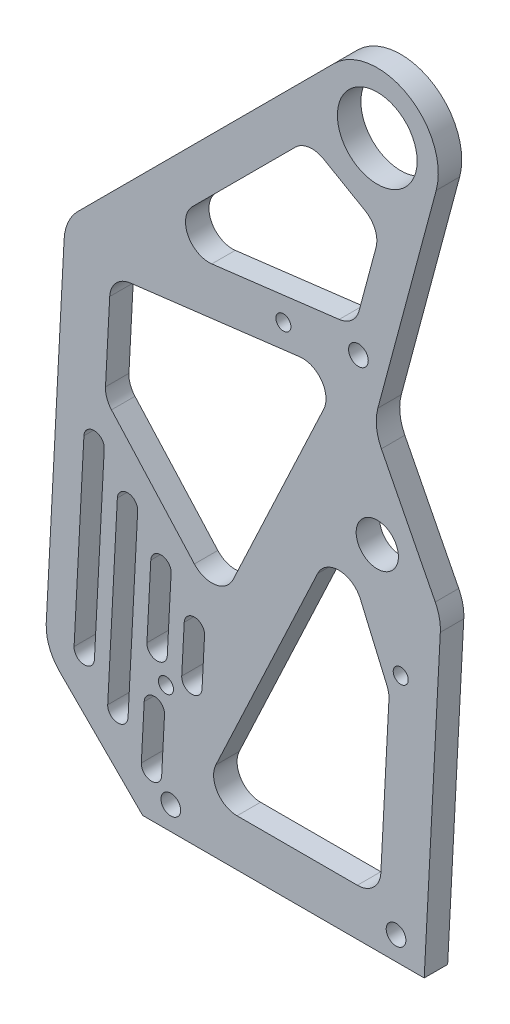
SolidWorks part; units mm, degrees
material "6061 Alloy"
ref_plane "Front Plane" through (0, 0, 0) normal (0, 0, 1) x (1, 0, 0)
ref_plane "Top Plane" through (0, 0, 0) normal (0, 1, 0) x (1, 0, 0)
ref_plane "Right Plane" through (0, 0, 0) normal (1, 0, 0) x (0, 0, -1)
sketch "Sketch1" plane through (0, 0, 0) normal (0, 0, 1) x (1, 0, 0)
  line L0 (0, 103.759) -> (0, -103.759) construction
  line L1 (-30, 76) -> (50, 76)
  line L2 (-30, 76) -> (-30, 256)
  line L3 (-30, 256) -> (50, 256)
  line L4 (50, 76) -> (50, 256)
  circle A0 centre (20, 226) radius 8.5
  dimension "D1" = 150
  dimension "D5" = 17
  dimension "D2" = 20
  dimension "D3" = 180
  dimension "D4" = 80
extrude "Boss-Extrude1" add sketch "Sketch1" along normal blind 5
sketch "Sketch2" plane through (0, 0, 5) normal (0, 0, 1) x (1, 0, 0)
  line L0 (20, 226) -> (20, 151) construction
  line L1 (20, 226) -> (-17.1819, 226) construction
  circle A0 centre (20, 151) radius 4.5
  dimension "D3" = 9
  dimension "D1" = 75
  dimension "D2" = 90
extrude "Cut-Extrude1" cut sketch "Sketch2" against normal blind 30
sketch "Sketch3" plane through (0, 0, 5) normal (0, 0, 1) x (1, 0, 0)
  circle A0 centre (0, 182) radius 1.6
  circle A1 centre (25, 129.3013) radius 1.6
  circle A2 centre (-25.0329, 102.5335) radius 1.6
  circle A3 centre (-15, 81) radius 2.5
  circle A4 centre (15, 81) radius 2.5
  circle A5 centre (24, 91) radius 2.5
  circle A6 centre (-24, 91) radius 2.5
  dimension "D1" = 5
  dimension "D2" = 3.2
extrude "Cut-Extrude2" cut sketch "Sketch3" against normal blind 5
sketch "Sketch4" plane through (0, 0, 5) normal (0, 0, 1) x (1, 0, 0)
  line L0 (10.8076, 235.1924) -> (-46.0411, 178.3437)
  line L1 (-46.0411, 178.3437) -> (-46.0411, 109.8941)
  line L2 (-46.0411, 109.8941) -> (-30, 76)
  line L3 (32.557, 222.6354) -> (22.7869, 186.1729)
  line L4 (22.7869, 186.1729) -> (30, 173.6795)
  line L5 (30, 173.6795) -> (30, 76)
  line L6 (-30, 76) -> (50, 76) construction
  line L7 (30, 76) -> (50, 76)
  line L8 (50, 76) -> (50, 256)
  line L9 (50, 256) -> (-30, 256)
  line L10 (-30, 256) -> (-68.6435, 166)
  line L11 (-68.6435, 166) -> (-57.2516, 84.4416)
  line L12 (-57.2516, 84.4416) -> (-30, 76)
  circle A0 centre (20, 226) radius 13
  circle A1 centre (20, 151) radius 4.5 construction
  line M14 (-30, 256) -> (-30, 76)
  line M15 (-30, 76) -> (50, 76)
  line M16 (50, 76) -> (50, 256)
  line M17 (50, 256) -> (-30, 256)
  dimension "D1" = 26
  dimension "D4" = 20
  dimension "D5" = 60
  dimension "D2" = 75
  dimension "D3" = 45
  dimension "D6" = 60
extrude "Cut-Extrude3" cut sketch "Sketch4" against normal blind 10 contours A0 L3 L4 L5 L0 M15 M16 M17 M14 region at (-10.989, 216.1814, 5)
sketch "Sketch5" plane through (0, 0, 5) normal (0, 0, 1) x (1, 0, 0)
  line L0 (-30, 194.3848) -> (-46.5355, 177.8492)
  line L1 (-48, 174.3137) -> (-48, 96.0711)
  line L2 (-46.5355, 92.5355) -> (-30, 76)
  line L4 (10.8076, 235.1924) -> (-30, 194.3848) construction
  line L6 (-30, 194.3848) -> (-30, 76) construction
  line L15 (-30, 76) -> (30, 76) construction
  line L16 (-35, 169.3848) -> (-35, 101) construction
  line L17 (-30, 169.3848) -> (-30, 101)
  line L18 (-40, 169.3848) -> (-40, 101)
  line L19 (-30, 138.6777) -> (-30, 121.7071)
  line L20 (-30, 138.6777) -> (-40, 148.6777)
  line L21 (-30, 121.7071) -> (-40, 131.7071)
  line L22 (-40, 148.6777) -> (-40, 131.7071)
  line L23 (-40, 148.6777) -> (-30, 121.7071)
  arc A0 (-30, 169.3848) -> (-40, 169.3848) centre (-35, 169.3848) ccw
  arc A1 (-40, 101) -> (-30, 101) centre (-35, 101) ccw
  arc A2 (-48, 96.0711) -> (-46.5355, 92.5355) centre (-43, 96.0711) ccw
  arc A3 (-46.5355, 177.8492) -> (-48, 174.3137) centre (-43, 174.3137) ccw
  point P14 (-35, 135.1924)
  point P26 (-48, 94)
  point P29 (-48, 176.3848)
  line M19 (-30, 194.3848) -> (-30, 76)
  dimension "D6" = 5
  dimension "D9" = 5
  dimension "D1" = 18
  dimension "D2" = 45
  dimension "D3" = 7
  dimension "D4" = 7
  dimension "D5" = 8
  dimension "D7" = 12
  dimension "D8" = 135
extrude "Boss-Extrude2" add sketch "Sketch5" against normal blind 5 contours L1 L2 L0 A1 L18 A0 L17 M19 | L16 L23 L18 L21 | L20 L16 L23 L17 | L16 L20 L23 | L23 L16 L21 region at (-40.982, 135.1924, 5) region at (-32.2222, 134.3002, 5) region at (-33.3333, 127.8689, 5) region at (-36.6667, 142.5159, 5) region at (-37.7778, 136.0845, 5)
fillet "Fillet1" radius 2 4 edges at (-40, 131.7071, 2.5) (-40, 148.6777, 2.5) (-30, 121.7071, 2.5) (-30, 138.6777, 2.5)
fillet "Fillet2" radius 5 2 edges at (30, 173.6795, 2.5) (22.7869, 186.1729, 2.5)
sketch "Sketch6" plane through (0, 0, 5) normal (0, 0, 1) x (1, 0, 0)
  line L0 (32.557, 222.6354) -> (23.323, 188.1734) construction
  line L1 (23.8225, 184.3793) -> (29.3301, 174.8397) construction
  circle A0 centre (15.9821, 183.9592) radius 2.1
  dimension "D1" = 4.2
  dimension "D2" = 6
  dimension "D3" = 7
extrude "Cut-Extrude4" cut sketch "Sketch6" against normal blind 5
sketch "Sketch7" plane through (0, 0, 5) normal (0, 0, 1) x (1, 0, 0)
  line L0 (30, 172.3397) -> (30, 76) construction
  line L1 (-30, 76) -> (30, 76)
  line L2 (-30, 76) -> (-30, 95.778)
  line L3 (-30, 95.778) -> (30, 95.778)
  line L4 (30, 76) -> (30, 95.778)
extrude "Boss-Extrude3" add sketch "Sketch7" against normal blind 5
sketch "Sketch8" plane through (0, 0, 5) normal (0, 0, 1) x (1, 0, 0)
  line L0 (-30, 169.3848) -> (-30, 143.5061) construction
  line L1 (-30, 76) -> (30, 76) construction
  circle A0 centre (-24, 81) radius 2.1
  circle A1 centre (24, 81) radius 2.1
  dimension "D1" = 4.2
  dimension "D2" = 6
  dimension "D3" = 54
  dimension "D4" = 5
extrude "Cut-Extrude6" cut sketch "Sketch8" against normal blind 5
sketch "Sketch9" plane through (0, 0, 5) normal (0, 0, 1) x (1, 0, 0)
  line L0 (18.046, 201.8387) -> (15.6185, 192.779)
  line L1 (1.2774, 211.52) -> (-13.5494, 196.6932)
  line L2 (11.0087, 189.078) -> (-9.7941, 188.1625)
  line L3 (-40, 126.8787) -> (-40, 101) construction
  arc A0 (8.1878, 211.6737) -> (14.7239, 207.9001) centre (20, 224.5858) ccw
  arc A1 (8.1878, 211.6737) -> (1.2774, 211.52) centre (4.8129, 207.9845) ccw
  arc A2 (14.7239, 207.9001) -> (18.046, 201.8387) centre (13.2164, 203.1328) cw
  arc A3 (-13.5494, 196.6932) -> (-9.7941, 188.1625) centre (-10.0139, 193.1577) ccw
  arc A4 (15.6185, 192.779) -> (11.0087, 189.078) centre (10.7889, 194.0731) cw
  dimension "D1" = 17.5
  dimension "D2" = 5
  dimension "D3" = 26.4506
  dimension "D4" = 29.9861
  dimension "D5" = 30.2059
  dimension "D6" = 41.2774
  dimension "D7" = 48.1878
  dimension "D8" = 50.7889
  dimension "D9" = 53.2164
  dimension "D10" = 18.7778
extrude "Cut-Extrude7" cut sketch "Sketch9" against normal blind 5
sketch "Sketch10" plane through (0, 0, 5) normal (0, 0, 1) x (1, 0, 0)
  line L0 (-20, 175.0528) -> (-20, 110.5916)
  line L1 (-20, 110.5916) -> (16.0369, 175.0528)
  line L2 (16.0369, 175.0528) -> (-20, 175.0528)
  line L3 (12.3296, 143.8296) -> (-20, 86)
  line L4 (-20, 86) -> (18, 86)
  line L5 (18, 86) -> (18, 140.6922)
  line L7 (-30, 76) -> (30, 76) construction
  line L8 (-30, 169.3848) -> (-30, 143.5061) construction
  line L9 (30, 172.3397) -> (30, 76) construction
  arc A0 (12.3296, 143.8296) -> (18, 140.6922) centre (20, 151) ccw
  circle A1 centre (20, 151) radius 4.5 construction
  circle A2 centre (20, 151) radius 4.5 construction
  dimension "D5" = 6
  dimension "D1" = 10
  dimension "D2" = 12
  dimension "D3" = 10
  dimension "D4" = 12
extrude "Cut-Extrude8" cut sketch "Sketch10" against normal blind 10
fillet "Fillet3" radius 5 5 edges at (18, 86, 2.5) (-20, 86, 2.5) (-20, 110.5916, 2.5) (16.0369, 175.0528, 2.5) (-20, 175.0528, 2.5)
fillet "Fillet4" radius 3 2 edges at (18, 140.6922, 2.5) (12.3296, 143.8296, 2.5)
sketch "Sketch11" plane through (0, 0, 5) normal (0, 0, 1) x (1, 0, 0)
  line L0 (23.323, 188.1734) -> (19.1312, 172.5294)
  line L1 (19.1312, 172.5294) -> (33.5734, 144.1849)
  line L2 (33.5734, 144.1849) -> (30, 76)
  line L3 (30, 76) -> (30, 151.1981)
  line L4 (30, 172.3397) -> (30, 76) construction
  line L5 (-46.5355, 177.8492) -> (-50.784, 96.784)
  line L6 (-50.784, 96.784) -> (-46.5355, 92.5355)
  line L7 (-46.5355, 92.5355) -> (-46.5355, 177.8492)
  line L8 (32.557, 222.6354) -> (23.323, 188.1734) construction
  line L9 (-46.5355, 92.5355) -> (-30, 76) construction
  circle A0 centre (20, 151) radius 4.5 construction
  dimension "D1" = 3
  dimension "D2" = 9
  dimension "D3" = 30
extrude "Boss-Extrude4" add sketch "Sketch11" against normal blind 5 contours L3 L2 L1 | L6 L7 L5 region at (31.1911, 123.7943, 5) region at (-47.9517, 122.3896, 5)
sketch "Sketch12" plane through (0, 0, 5) normal (0, 0, 1) x (1, 0, 0)
  line L0 (-48, 149.9056) -> (-46.5355, 177.8492)
  line L1 (10.8076, 235.1924) -> (-46.5355, 177.8492) construction
  line L2 (-46.5355, 177.8492) -> (-48, 176.3848)
  line L3 (-48, 176.3848) -> (-48, 149.9056)
  line L4 (-48, 174.3137) -> (-48, 149.9056) construction
  line L5 (-48, 149.9056) -> (-50.784, 96.784) construction
  line L6 (23.323, 188.1734) -> (19.1312, 172.5294)
  line L7 (19.1312, 172.5294) -> (30, 151.1981)
  line L8 (30, 151.1981) -> (30, 213.0924)
  line L9 (32.557, 222.6354) -> (23.323, 188.1734) construction
  line L10 (30, 213.0924) -> (23.323, 188.1734)
  line L11 (30, 151.1981) -> (33.5734, 144.1849) construction
extrude "Cut-Extrude9" cut sketch "Sketch12" against normal blind 5
sketch "Sketch13" plane through (0, 0, 5) normal (0, 0, 1) x (1, 0, 0)
  line L0 (-11.4765, 86) -> (13, 86) construction
  line L1 (18, 91) -> (18, 138.4601) construction
  line L2 (10.6232, 140.7773) -> (-15.8408, 93.4399) construction
  line L3 (-10.6357, 127.3421) -> (11.8776, 167.6129) construction
  line L4 (-20, 170.0528) -> (-20, 129.7819) construction
  line L5 (7.5133, 175.0528) -> (-15, 175.0528) construction
  line L6 (-9.7941, 188.1625) -> (11.0087, 189.078) construction
  line L7 (15.6185, 192.779) -> (18.046, 201.8387) construction
  line L8 (1.2774, 211.52) -> (-13.5494, 196.6932) construction
  line L9 (-20, 86) -> (18, 86)
  line L10 (18, 86) -> (18, 140.6922)
  line L11 (12.3296, 143.8296) -> (-20, 86)
  line L12 (-20, 110.5916) -> (16.0369, 175.0528)
  line L13 (-20, 175.0528) -> (-20, 110.5916)
  line L14 (16.0369, 175.0528) -> (-20, 175.0528)
  line L15 (-22.6456, 187.597) -> (14.67, 189.2391)
  line L16 (14.67, 189.2391) -> (19.4543, 207.0943)
  line L17 (5.1248, 215.3674) -> (-22.6456, 187.597)
  line L18 (-30, 169.3848) -> (-30, 143.5061) construction
  line L19 (-40, 169.3848) -> (-40, 149.5061) construction
  line L20 (-30, 169.3848) -> (-30, 101)
  line L21 (-40, 169.3848) -> (-40, 101)
  arc A0 (8.1878, 211.6737) -> (14.7239, 207.9001) centre (20, 224.5858) ccw construction
  arc A1 (5.1248, 215.3674) -> (19.4543, 207.0943) centre (20, 224.5858) ccw
  arc A2 (-40, 101) -> (-30, 101) centre (-35, 101) ccw construction
  arc A3 (-30, 169.3848) -> (-40, 169.3848) centre (-35, 169.3848) ccw construction
  arc A4 (-40, 101) -> (-30, 101) centre (-35, 101) ccw
  arc A5 (-30, 169.3848) -> (-40, 169.3848) centre (-35, 169.3848) ccw
  arc A6 (14.7436, 141.9104) -> (16.1111, 141.2467) centre (20, 151) ccw construction
  arc A7 (12.3296, 143.8296) -> (18, 140.6922) centre (20, 151) ccw
extrude "Boss-Extrude5" add sketch "Sketch13" against normal blind 5
sketch "Sketch14" plane through (0, 0, 5) normal (0, 0, 1) x (1, 0, 0)
  line L0 (5.2684, 218.3395) -> (-29.6708, 183.4002)
  line L1 (-29.6708, 183.4002) -> (15.2369, 188.9052)
  line L2 (15.2369, 188.9052) -> (20.7316, 209.4118)
  line L3 (20.7316, 209.4118) -> (5.2684, 218.3395)
  line L4 (-36.8047, 172.4509) -> (-38.0295, 149.0806)
  line L5 (-38.0295, 149.0806) -> (-13.9428, 122.3296)
  line L6 (-13.9428, 122.3296) -> (12.4456, 178.4882)
  line L7 (12.4456, 178.4882) -> (-36.8047, 172.4509)
  line L8 (12.0058, 149.3354) -> (-17.755, 86)
  line L9 (-17.755, 86) -> (20.5104, 86)
  line L10 (20.5104, 86) -> (22.5482, 124.885)
  line L11 (22.5482, 124.885) -> (12.0058, 149.3354)
  line L12 (33.5734, 144.1849) -> (30, 76) construction
  line L13 (10.8076, 235.1924) -> (-46.5355, 177.8492) construction
  line L14 (32.557, 222.6354) -> (19.1312, 172.5294) construction
  line L15 (-46.5355, 177.8492) -> (-50.784, 96.784) construction
  line L16 (20, 226) -> (13, 213.8756) construction
  line L17 (0, 182) -> (-0.6084, 186.9629) construction
  line L18 (0, 182) -> (0.6084, 177.0371) construction
  line L19 (15.9821, 183.9592) -> (15.3738, 188.922) construction
  line L20 (15.9821, 183.9592) -> (16.5905, 178.9963) construction
  line L21 (-30, 76) -> (30, 76) construction
  line L22 (-40.3533, 139.7057) -> (-42.4468, 99.7605) construction
  line L23 (-38.1863, 139.5921) -> (-40.2798, 99.6469)
  line L24 (-42.5204, 139.8192) -> (-44.6138, 99.8741)
  line L25 (-33.2278, 131.7919) -> (-35.2819, 92.5956) construction
  line L26 (-31.0607, 131.6783) -> (-33.1149, 92.4821)
  line L27 (-35.3948, 131.9055) -> (-37.449, 92.7092)
  line L28 (-27.5072, 97.0675) -> (-28.1171, 85.4308) construction
  line L29 (-25.3402, 96.9539) -> (-25.9501, 85.3172)
  line L30 (-29.6743, 97.181) -> (-30.2841, 85.5444)
  line L31 (-40.7876, 131.4195) -> (-33.2679, 131.0254) construction
  line L32 (-33.2679, 131.0254) -> (-25.7482, 130.6313) construction
  line L33 (-26.1022, 123.8781) -> (-26.9223, 108.2282) construction
  line L34 (-23.9351, 123.7646) -> (-24.7553, 108.1146)
  line L35 (-28.2692, 123.9917) -> (-29.0894, 108.3418)
  line L36 (-18.9766, 115.9644) -> (-19.5104, 105.7781) construction
  line L37 (-16.8095, 115.8508) -> (-17.3434, 105.6646)
  line L38 (-21.1436, 116.0779) -> (-21.6774, 105.8917)
  line L39 (-26.2388, 121.2703) -> (-18.7191, 120.8762) construction
  line L40 (-40.3533, 139.7057) -> (-18.9766, 115.9644) construction
  line L41 (-42.4468, 99.7605) -> (-28.1171, 85.4308) construction
  line L42 (-50.784, 96.784) -> (-30, 76) construction
  circle A0 centre (20, 226) radius 8.5 construction
  circle A2 centre (-24, 81) radius 2.1 construction
  circle A3 centre (20, 151) radius 4.5 construction
  circle A4 centre (25, 129.3013) radius 1.6 construction
  arc A5 (-38.1863, 139.5921) -> (-42.5204, 139.8192) centre (-40.3533, 139.7057) ccw
  arc A6 (-44.6138, 99.8741) -> (-40.2798, 99.6469) centre (-42.4468, 99.7605) ccw
  arc A7 (-31.0607, 131.6783) -> (-35.3948, 131.9055) centre (-33.2278, 131.7919) ccw
  arc A8 (-37.449, 92.7092) -> (-33.1149, 92.4821) centre (-35.2819, 92.5956) ccw
  arc A9 (-25.3402, 96.9539) -> (-29.6743, 97.181) centre (-27.5072, 97.0675) ccw
  arc A10 (-30.2841, 85.5444) -> (-25.9501, 85.3172) centre (-28.1171, 85.4308) ccw
  arc A11 (-23.9351, 123.7646) -> (-28.2692, 123.9917) centre (-26.1022, 123.8781) ccw
  arc A12 (-29.0894, 108.3418) -> (-24.7553, 108.1146) centre (-26.9223, 108.2282) ccw
  arc A13 (-16.8095, 115.8508) -> (-21.1436, 116.0779) centre (-18.9766, 115.9644) ccw
  arc A14 (-21.6774, 105.8917) -> (-17.3434, 105.6646) centre (-19.5104, 105.7781) ccw
  circle A15 centre (-25.0329, 102.5335) radius 1.6 construction
  point P33 (-41.4001, 119.7331)
  point P40 (-34.2548, 112.1938)
  point P55 (-27.8122, 91.2491)
  point P66 (-26.5122, 116.0532)
  point P73 (-19.2435, 110.8712)
  dimension "D13" = 2.17
  dimension "D1" = 14
  dimension "D2" = 8
  dimension "D3" = 8
  dimension "D4" = 10
  dimension "D5" = 10
  dimension "D6" = 12
  dimension "D7" = 10
  dimension "D8" = 10
  dimension "D9" = 8
  dimension "D10" = 8
  dimension "D11" = 4
  dimension "D12" = 6
  dimension "D14" = 7.53
  dimension "D15" = 8
  dimension "D16" = 8
  dimension "D17" = 6
  dimension "D18" = 6
  dimension "D19" = 10
  dimension "D20" = 45
  dimension "D21" = 40
extrude "Cut-Extrude10" cut sketch "Sketch14" against normal blind 5
fillet "Fillet5" radius 5 12 edges at (12.0058, 149.3354, 2.5) (22.5482, 124.885, 2.5) (-17.755, 86, 2.5) (20.5104, 86, 2.5) (-13.9428, 122.3296, 2.5) (-38.0295, 149.0806, 2.5) (-36.8047, 172.4509, 2.5) (12.4456, 178.4882, 2.5) (15.2369, 188.9052, 2.5) (-29.6708, 183.4002, 2.5) (20.7316, 209.4118, 2.5) (5.2684, 218.3395, 2.5)
fillet "Fillet6" radius 10 4 edges at (-50.784, 96.784, 2.5) (-46.5355, 177.8492, 2.5) (33.5734, 144.1849, 2.5) (19.1312, 172.5294, 2.5)
